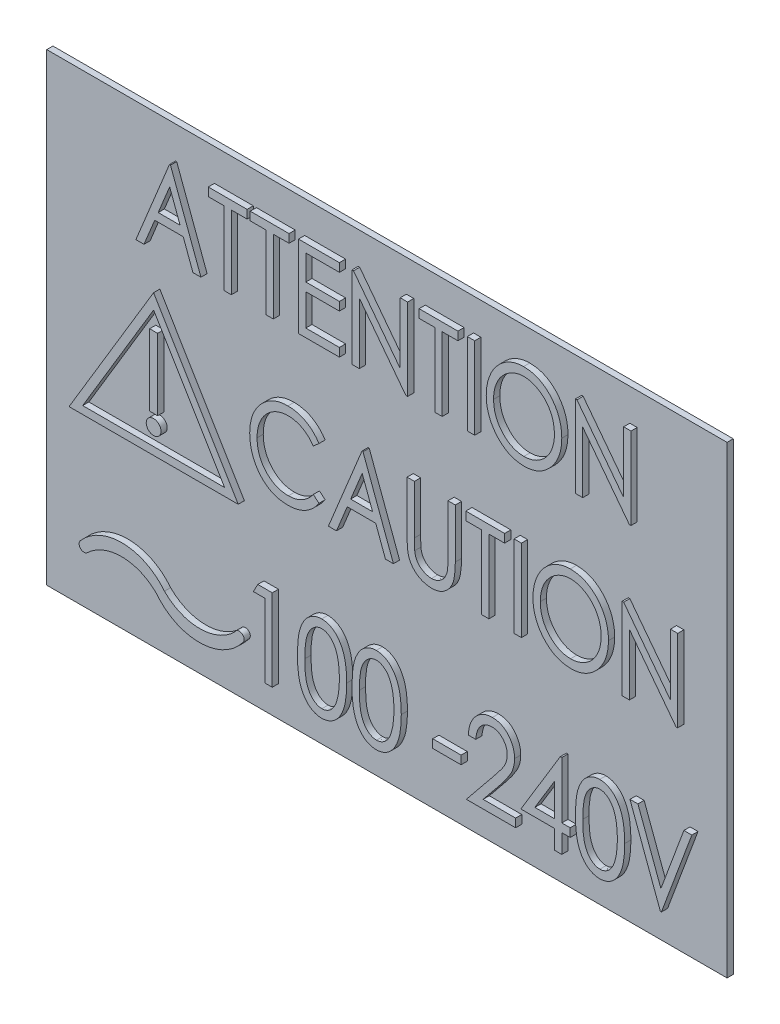
SolidWorks part; units mm, degrees
ref_plane "Plan de face" through (0, 0, 0) normal (0, 0, 1) x (1, 0, 0)
ref_plane "Plan de dessus" through (0, 0, 0) normal (0, 1, 0) x (1, 0, 0)
ref_plane "Plan de droite" through (0, 0, 0) normal (1, 0, 0) x (0, 0, -1)
sketch "Esquisse1" plane through (0, 0, 0) normal (0, 0, 1) x (1, 0, 0)
  line L1 (-32.0921, 1.0106) -> (-29.357, -3.5479)
  line L2 (-34.8271, -3.5479) -> (-29.357, -3.5479)
  line L3 (-34.8271, -3.5479) -> (-32.0921, 1.0106)
  line L6 (-32.0921, 0.5246) -> (-29.7985, -3.2979)
  line L7 (-34.3856, -3.2979) -> (-29.7985, -3.2979)
  line L8 (-34.3856, -3.2979) -> (-32.0921, 0.5246)
  dimension "D1" = 0.25
extrude "Extrusion1" add sketch "Esquisse1" along normal blind 0.2
sketch "Esquisse3" plane through (0, 0, 0) normal (0, 0, 1) x (1, 0, 0)
  arc A0 (-29.4645, -7.1758) -> (-29.2186, -7.3579) centre (-29.3223, -7.2408) cw
  arc A2 (-34.4498, -7.1067) -> (-34.2533, -7.3579) centre (-34.3414, -7.2244) ccw
  arc A3 (-32.0095, -7.3579) -> (-34.2533, -7.3579) centre (-33.1314, -8.4987) ccw
  arc A4 (-29.2186, -7.3579) -> (-32.0095, -7.3579) centre (-30.6141, -6.2854) cw
  arc A5 (-29.4645, -7.1758) -> (-31.7409, -7.1758) centre (-30.6027, -6.0512) cw
  arc A9 (-31.7409, -7.1758) -> (-34.4498, -7.1067) centre (-33.124, -8.2642) ccw
  dimension "D3" = 1.6
extrude "Extrusion3" add sketch "Esquisse3" along normal blind 0.2
sketch "Esquisse2" plane through (0, 0, 0) normal (0, 0, 1) x (1, 0, 0)
  line L0 (-31.9634, -0.0635) -> (-31.9634, -2.372)
  line L1 (-32.2208, -2.372) -> (-31.9634, -2.372)
  line L2 (-32.2208, -0.0635) -> (-32.2208, -2.372)
  line L3 (-32.2208, -0.0635) -> (-31.9634, -0.0635)
  line L10 (-32.0921, 0.1372) -> (-32.0921, -3.5215) construction
  circle A0 centre (-32.0921, -2.7536) radius 0.2387
extrude "Extrusion2" add sketch "Esquisse2" along normal blind 0.2
sketch "Esquisse4" plane through (0, 0, 0) normal (0, 0, 1) x (1, 0, 0)
  line L0 (-35.1244, -9.6525) -> (1.5083, -9.6525) construction
  text T0 "  100 -240V" font "Century Gothic" height in points 10
extrude "Extrusion4" add sketch "Esquisse4" along normal blind 0.2
sketch "Esquisse5" plane through (0, 0, 0) normal (0, 0, 1) x (1, 0, 0)
  line L1 (-35.7482, 5.8903) -> (-13.7482, 5.8903)
  line L2 (-35.7482, 5.8903) -> (-35.7482, -9.1097)
  line L3 (-35.7482, -9.1097) -> (-13.7482, -9.1097)
  line L4 (-13.7482, 5.8903) -> (-13.7482, -9.1097)
  dimension "D1" = 15
  dimension "D2" = 22
extrude "Extrusion5" add sketch "Esquisse5" against normal blind 0.2
sketch "Esquisse6" plane through (0, 0, 0) normal (0, 0, 1) x (1, 0, 0)
  text T0 "ATTENTION" font "Century Gothic" height in points 10
extrude "Extrusion6" add sketch "Esquisse6" along normal blind 0.2
sketch "Esquisse7" plane through (0, 0, 0) normal (0, 0, 1) x (1, 0, 0)
  text T0 "CAUTION" font "Century Gothic" height in points 10
extrude "Extrusion7" add sketch "Esquisse7" along normal blind 0.2
